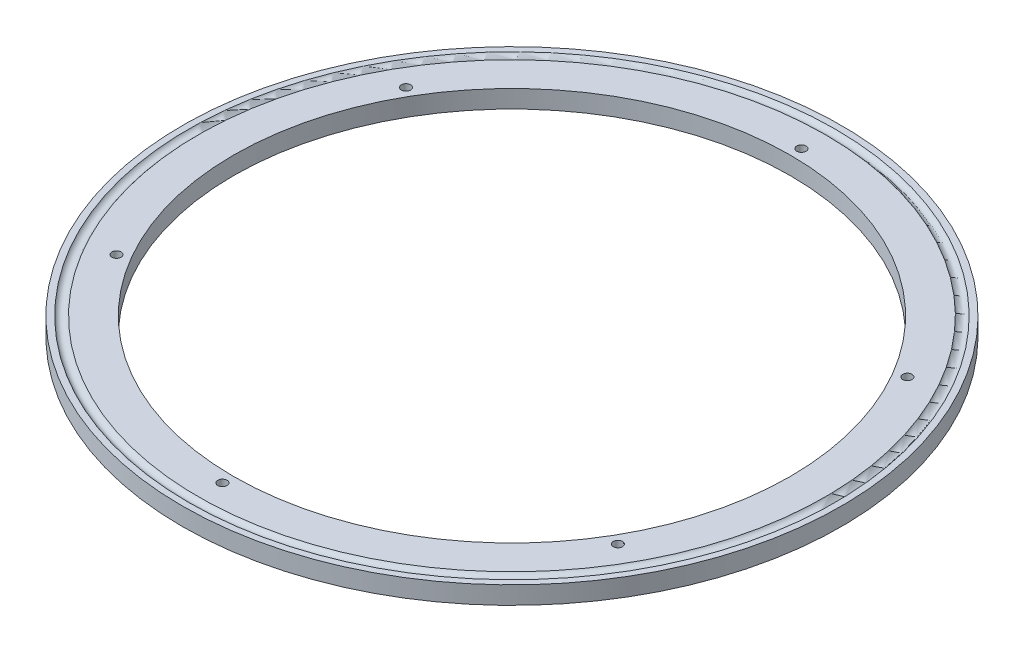
SolidWorks part; units mm, degrees
ref_plane "Front Plane" through (0, 0, 0) normal (0, 0, 1) x (1, 0, 0)
ref_plane "Top Plane" through (0, 0, 0) normal (0, 1, 0) x (1, 0, 0)
ref_plane "Right Plane" through (0, 0, 0) normal (1, 0, 0) x (0, 0, -1)
sketch "Sketch1" plane through (0, 0, 0) normal (0, 1, 0) x (1, 0, 0)
  circle A0 centre (0, 0) radius 79.375
  circle A1 centre (0, 0) radius 93.98
  circle A2 centre (0, 0) radius 90.805
  circle A3 centre (0, -82.55) radius 1.3208
  circle A4 centre (-71.4904, -41.275) radius 1.3208
  circle A5 centre (-71.4904, 41.275) radius 1.3208
  circle A6 centre (0, 82.55) radius 1.3208
  circle A7 centre (71.4904, 41.275) radius 1.3208
  circle A8 centre (71.4904, -41.275) radius 1.3208
  point P21 (0, 0)
  dimension "D1" = 158.75
  dimension "D4" = 2.6416
  dimension "D5" = 82.55
  dimension "D2" = 14.605
  dimension "D3" = 11.43
  dimension "D6" = 6
extrude "Boss-Extrude1" add sketch "Sketch1" along normal blind 5.08 contours A2 A0 | A1 A2 region at (-91.3218, 0, 0) region at (-88.2366, 0, 0)
sketch "Sketch2" plane through (0, 0, 0) normal (1, 0, 0) x (0, 0, -1)
  line L0 (-93.98, 0) -> (93.98, 0) construction
  line L1 (93.98, 5.08) -> (-93.98, 5.08) construction
  line L2 (-93.98, 0) -> (93.98, 0)
  line L3 (93.98, 5.08) -> (-93.98, 5.08)
  line L4 (89.5975, 4.318) -> (99.9841, 4.318) construction
  line L5 (95.9885, 2.54) -> (99.6739, 2.54) construction
  line L6 (0, 0) -> (0, 18.217) construction
  circle A0 centre (90.805, 5.9055) radius 1.5875 construction
  circle A1 centre (90.805, 5.969) radius 1.651
  circle A2 centre (90.805, -0.889) radius 1.651
  dimension "D3" = 3.175
  dimension "D4" = 3.302
  dimension "D1" = 90.805
  dimension "D2" = 0.762
  dimension "D5" = 2.54
revolve "Cut-Revolve1" cut sketch "Sketch2" angle 360 about L6 region at (0, 0.3118, -90.805) region at (0, 4.7682, -90.805)
equation "\"Middle Coupler Inner Daimeter\"= 6.25in"
equation "\"Middle Coupler  Wall Thickness\" = 0.25in"
equation "\"Middle Coupler Bottom Thickness\"= 0.2in"
equation "\"Bearing Rail Offset\"= 0.45in"
equation "\"3-56 UNF Tap\"= 0.089in"
equation "\"3-56 UNF Clearance\"= 0.104in"
equation "\"D5@Sketch1\"=(\"Middle Coupler Inner Daimeter\"*2+0.5)/4in"
equation "\"Ball Bearing Distance\"= 0.03in"
equation "\"D1@Sketch2\"=\"Middle Coupler Inner Daimeter\"/2+\"Bearing Rail Offset\""
equation "\"D3@Sketch1\"=\"Bearing Rail Offset\""
equation "\"D4@Sketch1\"=\"3-56 UNF Clearance\""
equation "\"D1@Sketch1\"=\"Middle Coupler Inner Daimeter\""
equation "\"D2@Sketch2\"=\"Ball Bearing Distance\""
equation "\"D4@Sketch2\"=\"D3@Sketch2\"+0.005"
equation "\"D5@Sketch2\"=\"Middle Coupler Bottom Thickness\"/2"
